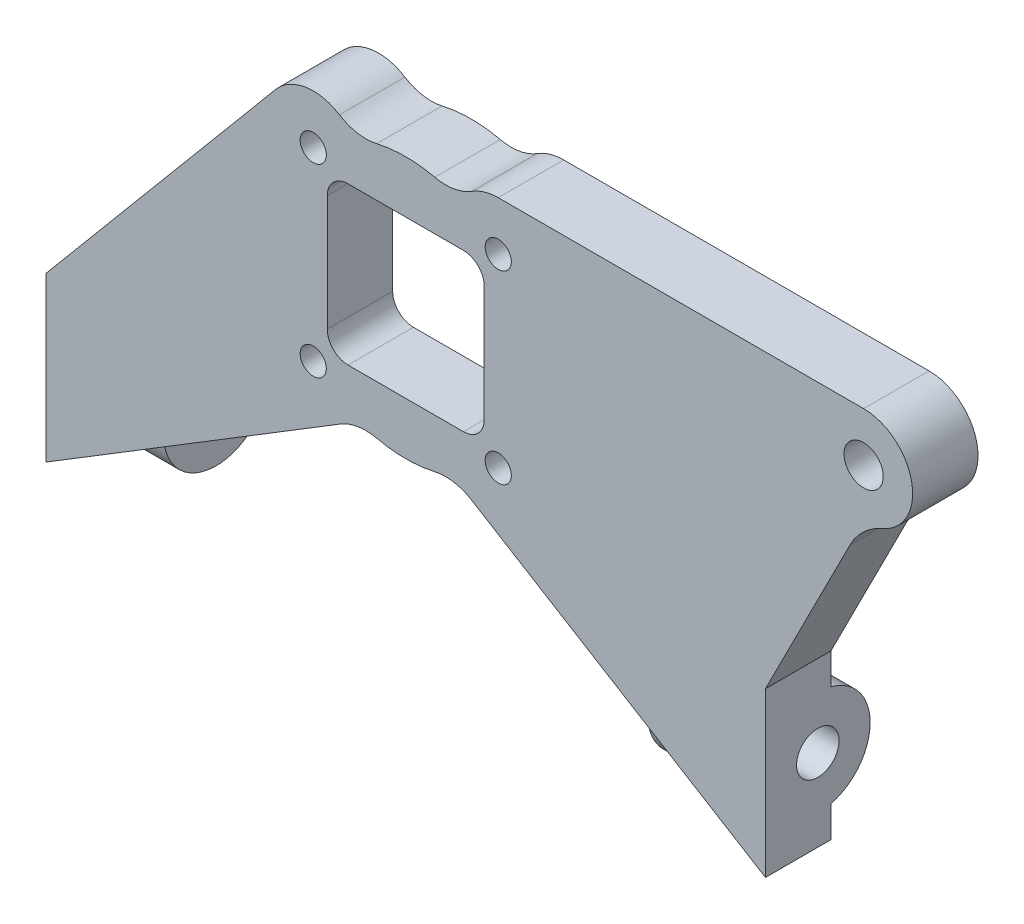
SolidWorks part; units mm, degrees
ref_plane "Front Plane" through (0, 0, 0) normal (0, 0, 1) x (1, 0, 0)
ref_plane "Top Plane" through (0, 0, 0) normal (0, 1, 0) x (1, 0, 0)
ref_plane "Right Plane" through (0, 0, 0) normal (1, 0, 0) x (0, 0, -1)
sketch "Sketch1" plane through (0, 0, 0) normal (0, 0, 1) x (1, 0, 0)
  line L0 (-19.8907, 18.9591) -> (-55, -22.9402)
  line L1 (19.8907, 18.9591) -> (55, -22.9402)
  line L2 (-55, -22.9402) -> (-55, -47.9402)
  line L3 (-55, -47.9402) -> (-10.2271, -20.5392)
  line L4 (8.825, 12) -> (-8.825, 12)
  line L5 (12, -8.825) -> (12, 8.825)
  line L6 (-8.825, -12) -> (8.825, -12)
  line L7 (-12, 8.825) -> (-12, -8.825)
  line L8 (8.825, 12) -> (-8.825, 12)
  line L9 (12, -8.825) -> (12, 8.825)
  line L10 (-8.825, -12) -> (8.825, -12)
  line L11 (-12, 8.825) -> (-12, -8.825)
  line L12 (10.2271, -20.5392) -> (55, -47.9402)
  line L13 (55, -47.9402) -> (55, -22.9402)
  line L14 (70, 379.5598) -> (70, -20.4402) construction
  line L15 (14.1421, 21.6421) -> (70, 21.6421)
  line L16 (70, 6.6421) -> (55, -22.9402)
  line L30 (66.0606, -20.4402) -> (73.9393, -20.4402)
  line L31 (73.9393, -20.4402) -> (73.9393, 379.5598)
  line L32 (73.9393, 379.5598) -> (66.0606, 379.5598)
  line L33 (66.0606, 379.5598) -> (66.0606, -20.4402)
  line L34 (66.0606, -20.4402) -> (73.9393, -20.4402)
  line L35 (73.9393, -20.4402) -> (73.9393, 379.5598)
  line L36 (73.9393, 379.5598) -> (66.0606, 379.5598)
  line L37 (66.0606, 379.5598) -> (66.0606, -20.4402)
  circle A0 centre (-14.1421, 14.1421) radius 2 construction
  circle A1 centre (14.1421, 14.1421) radius 2 construction
  circle A2 centre (14.1421, -14.1421) radius 2 construction
  circle A3 centre (-14.1421, -14.1421) radius 2 construction
  circle A4 centre (-14.1421, 14.1421) radius 2
  circle A5 centre (14.1421, 14.1421) radius 2
  circle A6 centre (14.1421, -14.1421) radius 2
  circle A7 centre (-14.1421, -14.1421) radius 2
  circle A9 centre (70, 14.1421) radius 3
  circle A10 centre (70, 14.1421) radius 7.5
  arc A13 (-8.825, 12) -> (-12, 8.825) centre (-8.825, 8.825) ccw
  arc A14 (12, 8.825) -> (8.825, 12) centre (8.825, 8.825) ccw
  arc A15 (8.825, -12) -> (12, -8.825) centre (8.825, -8.825) ccw
  arc A16 (-4.4455, -19.4997) -> (4.4455, -19.4997) centre (0, 0) ccw
  arc A17 (10.1274, -20.4771) -> (4.4455, -19.4997) centre (6.1126, -26.812) ccw
  arc A18 (10.1274, -20.4771) -> (20.4771, -10.1274) centre (14.1421, -14.1421) ccw
  arc A19 (19.4997, -4.4455) -> (20.4771, -10.1274) centre (26.812, -6.1126) ccw
  arc A20 (19.4997, -4.4455) -> (19.4997, 4.4455) centre (0, 0) ccw
  arc A21 (20.4771, 10.1274) -> (19.4997, 4.4455) centre (26.812, 6.1126) ccw
  arc A22 (20.4771, 10.1274) -> (10.1274, 20.4771) centre (14.1421, 14.1421) ccw
  arc A23 (4.4455, 19.4997) -> (10.1274, 20.4771) centre (6.1126, 26.812) ccw
  arc A24 (4.4455, 19.4997) -> (-4.4455, 19.4997) centre (0, 0) ccw
  arc A25 (-10.1274, 20.4771) -> (-4.4455, 19.4997) centre (-6.1126, 26.812) ccw
  arc A26 (-10.1274, 20.4771) -> (-20.4771, 10.1274) centre (-14.1421, 14.1421) ccw
  arc A27 (-19.4997, 4.4455) -> (-20.4771, 10.1274) centre (-26.812, 6.1126) ccw
  arc A28 (-19.4997, 4.4455) -> (-19.4997, -4.4455) centre (0, 0) ccw
  arc A29 (-20.4771, -10.1274) -> (-19.4997, -4.4455) centre (-26.812, -6.1126) ccw
  arc A30 (-20.4771, -10.1274) -> (-10.1274, -20.4771) centre (-14.1421, -14.1421) ccw
  arc A31 (-4.4455, -19.4997) -> (-10.1274, -20.4771) centre (-6.1126, -26.812) ccw
  arc A32 (-4.4455, -19.4997) -> (4.4455, -19.4997) centre (0, 0) ccw
  arc A33 (10.1274, -20.4771) -> (4.4455, -19.4997) centre (6.1126, -26.812) ccw
  arc A34 (10.1274, -20.4771) -> (20.4771, -10.1274) centre (14.1421, -14.1421) ccw
  arc A35 (19.4997, -4.4455) -> (20.4771, -10.1274) centre (26.812, -6.1126) ccw
  arc A36 (19.4997, -4.4455) -> (19.4997, 4.4455) centre (0, 0) ccw
  arc A37 (20.4771, 10.1274) -> (19.4997, 4.4455) centre (26.812, 6.1126) ccw
  arc A38 (20.4771, 10.1274) -> (10.1274, 20.4771) centre (14.1421, 14.1421) ccw
  arc A39 (4.4455, 19.4997) -> (10.1274, 20.4771) centre (6.1126, 26.812) ccw
  arc A40 (4.4455, 19.4997) -> (-4.4455, 19.4997) centre (0, 0) ccw
  arc A41 (-10.1274, 20.4771) -> (-4.4455, 19.4997) centre (-6.1126, 26.812) ccw
  arc A42 (-10.1274, 20.4771) -> (-20.4771, 10.1274) centre (-14.1421, 14.1421) ccw
  arc A43 (-19.4997, 4.4455) -> (-20.4771, 10.1274) centre (-26.812, 6.1126) ccw
  arc A44 (-19.4997, 4.4455) -> (-19.4997, -4.4455) centre (0, 0) ccw
  arc A45 (-20.4771, -10.1274) -> (-19.4997, -4.4455) centre (-26.812, -6.1126) ccw
  arc A46 (-20.4771, -10.1274) -> (-10.1274, -20.4771) centre (-14.1421, -14.1421) ccw
  arc A47 (-4.4455, -19.4997) -> (-10.1274, -20.4771) centre (-6.1126, -26.812) ccw
  arc A48 (-12, -8.825) -> (-8.825, -12) centre (-8.825, -8.825) ccw
  arc A49 (-8.825, 12) -> (-12, 8.825) centre (-8.825, 8.825) ccw
  arc A50 (12, 8.825) -> (8.825, 12) centre (8.825, 8.825) ccw
  arc A51 (8.825, -12) -> (12, -8.825) centre (8.825, -8.825) ccw
  arc A52 (-12, -8.825) -> (-8.825, -12) centre (-8.825, -8.825) ccw
  dimension "D5" = 6
  dimension "D3" = 25
  dimension "D1" = 0
  dimension "D2" = 0
  dimension "D4" = 0
extrude "Boss-Extrude1" add sketch "Sketch1" along normal blind 10 contours A46 A45 A44 A43 A42 L0 L2 L3 | A47 A32 A33 A34 A35 A36 A37 A38 A39 A40 A41 A42 A43 A44 A45 A46 A52 L11 A49 L8 A50 L9 A51 L10 A7 A6 A5 A4 | A38 A37 A36 A35 A34 L12 L13 L1 | A38 L1 L16 A10 L15 | A10 L15 | A10 L37 L16 | L37 A10 | L14 A10 L37 A9 | A10 L14 A9 L35 | L35 A10 region at (-35.6197, -18.4256, 0) region at (-15.2003, 20.9482, 0) region at (47.4207, 5.7873, 0) region at (67.0302, 21.3115, 0) region at (35.6197, -18.4256, 0) region at (72.0051, 21.2081, 0) region at (69.8449, 19.3921, 0) region at (64.6027, 14.1421, 0) region at (75.3972, 14.1421, 0) region at (67.3446, 4.3006, 0)
fillet "Fillet1" radius 10 1 edges at (70, 6.6421, 5)
sketch "Sketch2" plane through (55, 0, 0) normal (1, 0, 0) x (0, 0, -1)
  line L0 (-10, -35.4402) -> (0, -35.4402) construction
  line L1 (-10, -47.9402) -> (-10, -22.9402) construction
  line L2 (0, -47.9402) -> (0, -22.9402) construction
  circle A2 centre (-2, -35.4402) radius 8
  dimension "D1" = 16
extrude "Boss-Extrude4" add sketch "Sketch2" against normal blind 18
sketch "Sketch5" plane through (37, 0, 0) normal (-1, 0, 0) x (0, 0, 1)
  circle A0 centre (2, -35.4402) radius 5
  dimension "D1" = 10
extrude "Cut-Extrude3" cut sketch "Sketch5" along normal up to next
sketch "Sketch6" plane through (37, 0, 0) normal (-1, 0, 0) x (0, 0, 1)
  circle A0 centre (2, -35.4402) radius 3.25
  dimension "D1" = 6.5
extrude "Cut-Extrude4" cut sketch "Sketch6" against normal up to next
mirror "Mirror2" about plane through (0, 0, 0) normal (1, 0, 0) of "Cut-Extrude4", "Cut-Extrude3", "Boss-Extrude4"
